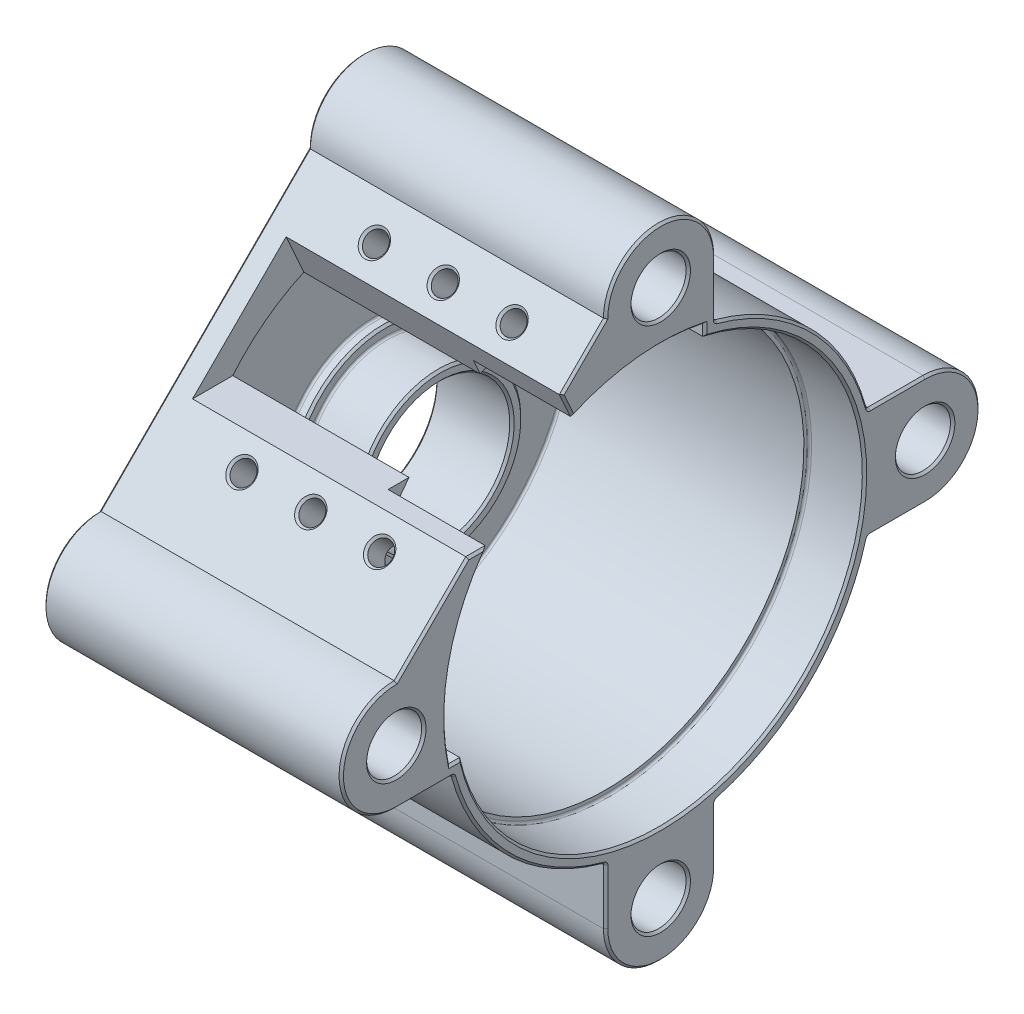
SolidWorks part; units mm, degrees
material "1060 Сплав"
ref_plane "Спереди" through (0, 0, 0) normal (0, 0, 1) x (1, 0, 0)
ref_plane "Сверху" through (0, 0, 0) normal (0, 1, 0) x (1, 0, 0)
ref_plane "Справа" through (0, 0, 0) normal (1, 0, 0) x (0, 0, -1)
sketch "Эскиз1" plane through (0, 0, 0) normal (0, 0, 1) x (1, 0, 0)
  line L0 (0, 0) -> (26039.5549, 0) construction
  line L1 (-25, 7.5) -> (-25, 8.5)
  line L2 (0, 19.5) -> (-27, 19.5)
  line L3 (-27, 19.5) -> (-27, 6.5)
  line L4 (-27, 6.5) -> (-20, 6.5)
  line L5 (-20, 6.5) -> (-20, 7.5)
  line L6 (-20, 7.5) -> (-25, 7.5)
  line L7 (-26, 8.5) -> (-26, 18)
  line L8 (-26, 18) -> (-5, 18)
  line L9 (-5, 18) -> (-5, 18.5)
  line L10 (-5, 18.5) -> (0, 18.5)
  line L11 (0, 18.5) -> (0, 19.5)
  line L12 (-25, 8.5) -> (-26, 8.5)
  dimension "D1" = 18.5
  dimension "D2" = 1
  dimension "D3" = 18
  dimension "D4" = 5
  dimension "D5" = 21
  dimension "D6" = 1
  dimension "D7" = 1
  dimension "D8" = 1
  dimension "D9" = 7.5
  dimension "D10" = 1
  dimension "D11" = 13
  dimension "D12" = 0.5
  dimension "D13" = 5
revolve "Повернуть1" add sketch "Эскиз1" angle 360 about L0
sketch "Эскиз5" plane through (0, 0, 0) normal (1, 0, 0) x (0, 0, -1)
  line L0 (0, 0) -> (0, -24) construction
  line L1 (5, -24) -> (5, -18.8481)
  line L2 (-5, -24) -> (-5, -18.8481)
  line L3 (-24, -5) -> (-18.8481, -5)
  line L5 (0, 0) -> (-24, 0) construction
  line L7 (5, 24) -> (5, 18.8481)
  line L8 (0, 0) -> (0, 24) construction
  line L9 (24, 5) -> (18.8481, 5)
  line L10 (24, -5) -> (18.8481, -5)
  line L11 (0, 0) -> (24, 0) construction
  line L12 (-24, 5) -> (-5, 24)
  line L14 (-24, 5) -> (-18.8481, 5) [skipped]
  line L15 (-5, 24) -> (-5, 18.8481) [skipped]
  circle A0 centre (0, -24) radius 2.5
  arc A1 (5, -24) -> (-5, -24) centre (0, -24) cw
  arc A2 (5, -18.8481) -> (-5, -18.8481) centre (0, 0) cw
  circle A3 centre (0, 0) radius 19.5 construction
  circle A5 centre (-24, 0) radius 2.5
  arc A6 (-24, -5) -> (-24, 5) centre (-24, 0) cw
  arc A7 (-18.8481, -5) -> (-5, 18.8481) centre (0, 0) cw
  circle A8 centre (0, 24) radius 2.5
  arc A9 (-5, 24) -> (5, 24) centre (0, 24) cw
  arc A10 (-5, 18.8481) -> (5, 18.8481) centre (0, 0) cw
  circle A11 centre (24, 0) radius 2.5
  arc A12 (24, 5) -> (24, -5) centre (24, 0) cw
  arc A13 (18.8481, 5) -> (18.8481, -5) centre (0, 0) cw
  point P32 (0, 0)
  dimension "D2" = 5
  dimension "D3" = 5
  dimension "D4" = 19.5
  dimension "D1" = 24
  dimension "D5" = 5.1519
  dimension "D6" = 5.1519
  dimension "D7" = 4
extrude "Бобышка-Вытянуть2" add sketch "Эскиз5" against normal through all
sketch "Эскиз2" plane through (0, 0, 0) normal (1, 0, 0) x (0, 0, -1)
  line L0 (0, 0) -> (0, 50000) construction
  line L1 (4, 19.0853) -> (4, 16.5227)
  line L2 (4, 0) -> (4, 50000) construction
  line L3 (0, 0) -> (0, -4) construction
  line L4 (0, -4) -> (-50000, -4) construction
  line L5 (-19.0853, -4) -> (-16.5227, -4)
  line L6 (-4, 0) -> (-4, 50000) construction
  arc A0 (4, 16.5227) -> (-16.5227, -4) centre (0, 0) ccw
  arc A1 (-19.0853, -4) -> (4, 19.0853) centre (0, 0) cw
  circle A2 centre (0, 0) radius 19.5 construction
  dimension "D3" = 17
  dimension "D4" = 19.5
  dimension "D1" = 4
  dimension "D2" = 4
  dimension "D5" = 2.5626
  dimension "D6" = 2.5626
  dimension "D7" = 16.5227
extrude "Вырез-Вытянуть1" cut sketch "Эскиз2" against normal blind 9 contours A0 L5 A1 L1
sketch "Эскиз3" plane through (0, 0, 0) normal (1, 0, 0) x (0, 0, -1)
  line L3 (-40, 11.5) -> (-12.52, 11.5)
  line L4 (0, 0) -> (-20535.6471, 45588.2353) construction
  line L5 (-6.9821, 15.5) -> (-13.2408, 29.394)
  line L6 (-13.2408, 29.394) -> (-40, 11.5)
  line L7 (0, 15.5) -> (-50000, 15.5) construction
  circle A0 centre (0, 0) radius 15.5 construction
  circle A1 centre (0, 0) radius 11.5 construction
  arc A2 (-6.9821, 15.5) -> (-12.52, 11.5) centre (0, 0) ccw
  dimension "D1" = 31
  dimension "D2" = 23
  dimension "D4" = 34
  dimension "D3" = 15.2386
  dimension "D5" = 32.1908
extrude "Вырез-Вытянуть2" cut sketch "Эскиз3" against normal blind 25
sketch "Эскиз6" plane through (0, 14.5, 14.5) normal (0, 0.7071, 0.7071) x (1, 0, 0)
  line L0 (-25, -4.2426) -> (0, 7.7692) construction
  line L1 (-12.5, 1.7633) -> (-50012.5, 1.7633) construction
  circle A0 centre (-18.75, 10.2633) radius 1
  circle A1 centre (-12.5, 10.2633) radius 1
  circle A2 centre (-6.25, 10.2633) radius 1
  circle A3 centre (-6.25, -6.7367) radius 1
  circle A4 centre (-12.5, -6.7367) radius 1
  circle A5 centre (-18.75, -6.7367) radius 1
  point P6 (-12.5, 1.7633)
  dimension "D2" = 2
  dimension "D5" = 6.25
  dimension "D1" = 8.5
  dimension "D3" = 18.75
  dimension "D4" = 3
extrude "Вырез-Вытянуть4" cut sketch "Эскиз6" against normal blind 10
fillet "Скругление1" radius 0.2 10 edges at (-13.5, -5, 18.8481) (-13.5, -18.8481, 5) (-13.5, -18.8481, -5) (-13.5, -5, -18.8481) (-13.5, 18.8481, -5) (-13.5, 5, -18.8481) (-5, -13.0815, -13.0815) (-25, 0, 7.5) (-26, 0, 8.5) (-26, 0, 18)
chamfer "Фаска1" distance 0.2 angle 45 60 edges at (-27, 0, -26.5) (-27, 0, 21.5) (-27, 24, -2.5) (-27, -24, -2.5) (-27, -29, 0) (-27, -21.5007, -5) (-27, -18.88, -5.041) (-27, -13.7886, -13.7886) (-27, -5.041, -18.88) (-27, -5, -21.5007) (-27, 0, -29) (-27, 5, -21.5007) (-27, 5.041, -18.88) (-27, 13.7886, -13.7886) (-27, 18.88, -5.041) (-27, 21.5007, -5) (-27, 29, 0) (-27, 14.5, 14.5) (-27, 0, 29) (-27, -5, 21.5007) (-27, -5.041, 18.88) (-27, -13.7886, 13.7886) (-27, -18.88, 5.041) (-27, -21.5007, 5) (-27, 0, 6.5) (-20, 0, 6.5) (-20, 0, 7.5) (0, 0, -26.5) (0, 0, 21.5) (0, 24, -2.5) (0, -24, -2.5) (0, 29, 0) (0, 21.5007, -5) (0, 18.88, -5.041) (0, 13.7886, -13.7886) (0, 5.041, -18.88) (0, 5, -21.5007) (0, 0, -29) (0, -5, -21.5007) (0, -5.041, -18.88) (0, -13.7886, -13.7886) (0, -18.88, -5.041) (0, -21.5007, -5) (0, -29, 0) (0, -21.5007, 5) (0, -18.88, 5.041) (0, -13.7886, 13.7886) (0, -5.041, 18.88) (0, -5, 21.5007) (0, 0, 29) (0, 8.25, 20.75) (0, 11.5, 16.624) (0, 4.1045, 19.0631) (0, -4, 18.5739) (0, -13.0815, -13.0815) (0, 18.5739, -4) (0, 19.3857, 2.1081) (0, 18.8865, 8.5076) (0, 21.9968, 7.0032) (-25, 0, 8.5)
chamfer "Фаска2" distance 0.2 angle 45 6 edges at (-6.25, 21.0501, 7.9499) (-12.5, 21.0501, 7.9499) (-18.75, 21.0501, 7.9499) (-18.75, 10.4435, 18.5565) (-12.5, 10.4435, 18.5565) (-6.25, 10.4435, 18.5565)
